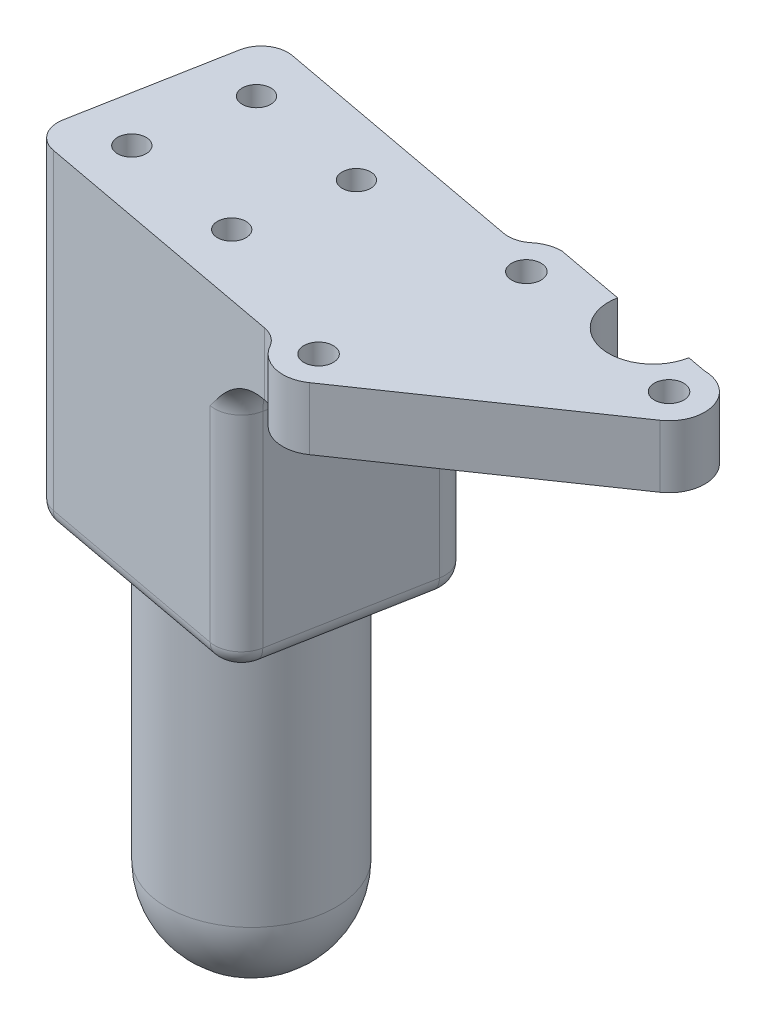
SolidWorks part; units mm, degrees
ref_plane "Front Plane" through (0, 0, 0) normal (0, 0, 1) x (1, 0, 0)
ref_plane "Top Plane" through (0, 0, 0) normal (0, 1, 0) x (1, 0, 0)
ref_plane "Right Plane" through (0, 0, 0) normal (1, 0, 0) x (0, 0, -1)
sketch "Sketch1" plane through (0, 0, 0) normal (0, 1, 0) x (1, 0, 0)
  line L0 (1.4975, 0.7868) -> (-36.9339, 98.5008) construction
  line L6 (-56.6569, 90.4835) -> (-36.9937, 86.8285)
  line L17 (-34.7298, 79.5308) -> (-58.048, 63.5226)
  line L18 (-61.6543, 88.9381) -> (-90.7933, 94.3545)
  line L19 (1.4975, 0.7868) -> (79.9099, 31.6269) construction
  line L20 (-94.291, 91.9533) -> (-97.3978, 75.2396)
  line L21 (-65.8576, 66.3255) -> (-94.9966, 71.7418)
  line L22 (6.159, 94.65) -> (23.8009, 118.4656) construction
  line L23 (9.5157, 132.7811) -> (23.176, 122.6619) construction
  line L24 (-12.3225, 108.3406) -> (5.3194, 132.1562) construction
  line L25 (-25.6246, 83.1119) -> (2.3512, 87.278) construction
  line L26 (-17.0338, 106.0675) -> (-28.9387, 89.9966) construction
  line L27 (59.6519, -88.9099) -> (39.9887, -85.2549) construction
  line L28 (37.7248, -77.9572) -> (61.043, -61.949) construction
  line L29 (64.6494, -87.3645) -> (93.7884, -92.7809) construction
  line L30 (97.2861, -90.3797) -> (100.3929, -73.666) construction
  line L31 (68.8527, -64.7518) -> (97.9916, -70.1682) construction
  line L32 (-3.1639, -93.0764) -> (-20.8058, -116.8919) construction
  line L33 (-6.5207, -131.2074) -> (-20.1809, -121.0883) construction
  line L34 (15.3176, -106.767) -> (-2.3243, -130.5825) construction
  line L35 (28.6196, -81.5383) -> (0.6438, -85.7043) construction
  line L36 (20.0288, -104.4939) -> (31.9337, -88.423) construction
  circle A33 centre (-56.6569, 86.4835) radius 1.65
  circle A34 centre (-36.9937, 82.8285) radius 1.65
  circle A35 centre (-40.6487, 63.1653) radius 1.65 construction
  circle A36 centre (-60.3119, 66.8203) radius 1.65
  arc A37 (-56.6569, 90.4835) -> (-59.1993, 89.5716) centre (-56.6569, 86.4835) ccw
  arc A38 (-34.7298, 79.5308) -> (-36.9937, 86.8285) centre (-36.9937, 82.8285) ccw
  arc A39 (-63.7941, 64.8521) -> (-58.048, 63.5226) centre (-60.3119, 66.8203) ccw
  arc A40 (-65.8576, 66.3255) -> (-63.7941, 64.8521) centre (-66.4058, 63.376) cw
  arc A41 (-59.1993, 89.5716) -> (-61.6543, 88.9381) centre (-61.1061, 91.8876) cw
  arc A42 (-90.7933, 94.3545) -> (-94.291, 91.9533) centre (-91.3416, 91.405) ccw
  arc A43 (-94.9966, 71.7418) -> (-97.3978, 75.2396) centre (-94.4483, 74.6913) cw
  arc A44 (23.8009, 118.4656) -> (23.176, 122.6619) centre (21.3903, 120.2513) ccw construction
  arc A45 (5.3194, 132.1562) -> (9.5157, 132.7811) centre (7.73, 130.3704) cw construction
  arc A46 (-14.5513, 107.1319) -> (-12.3225, 108.3406) centre (-14.7332, 110.1263) ccw construction
  arc A47 (6.159, 94.65) -> (5.6521, 92.1657) centre (8.5696, 92.8643) ccw construction
  arc A48 (5.6521, 92.1657) -> (2.3512, 87.278) centre (1.7621, 91.2343) cw construction
  arc A49 (-25.6246, 83.1119) -> (-28.9387, 89.9966) centre (-26.2137, 87.0683) cw construction
  arc A50 (-17.0338, 106.0675) -> (-14.5513, 107.1319) centre (-14.3088, 103.1392) cw construction
  circle A51 centre (1.7621, 91.2343) radius 1.65 construction
  circle A52 centre (-10.1428, 75.1634) radius 1.65 construction
  circle A53 centre (-26.2137, 87.0683) radius 1.65 construction
  circle A54 centre (-14.3088, 103.1392) radius 1.65 construction
  circle A55 centre (59.6519, -84.9099) radius 1.65 construction
  circle A56 centre (39.9887, -81.2549) radius 1.65 construction
  circle A57 centre (43.6437, -61.5917) radius 1.65 construction
  circle A58 centre (63.3069, -65.2467) radius 1.65 construction
  arc A59 (59.6519, -88.9099) -> (62.1943, -87.9979) centre (59.6519, -84.9099) ccw construction
  arc A60 (37.7248, -77.9572) -> (39.9887, -85.2549) centre (39.9887, -81.2549) ccw construction
  arc A61 (66.7892, -63.2785) -> (61.043, -61.949) centre (63.3069, -65.2467) ccw construction
  arc A62 (68.8527, -64.7518) -> (66.7892, -63.2785) centre (69.4009, -61.8024) cw construction
  arc A63 (62.1943, -87.9979) -> (64.6494, -87.3645) centre (64.1012, -90.314) cw construction
  arc A64 (93.7884, -92.7809) -> (97.2861, -90.3797) centre (94.3366, -89.8314) ccw construction
  arc A65 (97.9916, -70.1682) -> (100.3929, -73.666) centre (97.4434, -73.1177) cw construction
  arc A66 (-20.8058, -116.8919) -> (-20.1809, -121.0883) centre (-18.3952, -118.6777) ccw construction
  arc A67 (-2.3243, -130.5825) -> (-6.5207, -131.2074) centre (-4.7349, -128.7968) cw construction
  arc A68 (17.5464, -105.5582) -> (15.3176, -106.767) centre (17.7282, -108.5527) ccw construction
  arc A69 (-3.1639, -93.0764) -> (-2.657, -90.5921) centre (-5.5746, -91.2907) ccw construction
  arc A70 (-2.657, -90.5921) -> (0.6438, -85.7043) centre (1.233, -89.6607) cw construction
  arc A71 (28.6196, -81.5383) -> (31.9337, -88.423) centre (29.2088, -85.4947) cw construction
  arc A72 (20.0288, -104.4939) -> (17.5464, -105.5582) centre (17.3039, -101.5656) cw construction
  circle A73 centre (1.233, -89.6607) radius 1.65 construction
  circle A74 centre (13.1379, -73.5898) radius 1.65 construction
  circle A75 centre (29.2088, -85.4947) radius 1.65 construction
  circle A76 centre (17.3039, -101.5656) radius 1.65 construction
  dimension "D1" = 8
  dimension "D2" = 8
  dimension "D3" = 8
  dimension "D4" = 3
  dimension "D5" = 3
extrude "Boss-Extrude1" add sketch "Sketch1" along normal mid plane 7
sketch "Sketch3" plane through (0, -3.5, 0) normal (0, 1, 0) x (1, 0, 0)
  line L2 (-69.1638, 90.334) -> (-90.7933, 94.3545)
  line L3 (-61.6543, 88.9381) -> (-90.7933, 94.3545) construction
  line L4 (-94.291, 91.9533) -> (-97.3978, 75.2396)
  line L5 (-94.9966, 71.7418) -> (-73.3671, 67.7213)
  line L6 (-94.9966, 71.7418) -> (-65.8576, 66.3255) construction
  line L7 (-69.8693, 70.1226) -> (-66.7626, 86.8363)
  arc A0 (-90.7933, 94.3545) -> (-94.291, 91.9533) centre (-91.3416, 91.405) ccw
  arc A1 (-97.3978, 75.2396) -> (-94.9966, 71.7418) centre (-94.4483, 74.6913) ccw
  arc A2 (-73.3671, 67.7213) -> (-69.8693, 70.1226) centre (-72.8188, 70.6708) ccw
  arc A3 (-69.1638, 90.334) -> (-66.7626, 86.8363) centre (-69.7121, 87.3845) cw
  point P2 (-70.4176, 67.1731)
  point P19 (-66.2143, 89.7857)
  dimension "D2" = 3
  dimension "D1" = 28
extrude "Boss-Extrude3" add sketch "Sketch3" against normal blind 30
fillet "Fillet1" radius 5 3 edges at (-71.1209, -3.5, -68.1975) (-68.316, -3.5, -78.4794) (-67.2388, -3.5, -89.0824)
fillet "Fillet2" radius 2 8 edges at (-67.2388, -33.5, -89.0824) (-68.316, -33.5, -78.4794) (-71.1209, -33.5, -68.1975) (-84.1818, -33.5, -69.7316) (-96.9216, -33.5, -72.9934) (-95.8444, -33.5, -83.5964) (-93.0395, -33.5, -93.8783) (-79.9786, -33.5, -92.3443)
sketch "Sketch4" plane through (0, -33.5, 0) normal (0, -1, 0) x (-1, 0, 0)
  line L0 (93.8781, 83.2309) -> (70.2823, 78.8449) construction
  line L1 (92.3247, 91.5878) -> (95.4315, 74.8741) construction
  line L2 (71.8357, 70.4881) -> (68.7289, 87.2018) construction
  line L4 (69.5293, 88.3677) -> (91.1588, 92.3882) construction
  line L5 (80.3441, 90.3779) -> (83.8163, 71.6979) construction
  line L6 (94.6311, 73.7082) -> (73.0016, 69.6877) construction
  circle A0 centre (82.0802, 81.0379) radius 9.5
extrude "Boss-Extrude4" add sketch "Sketch4" along normal blind 30
fillet "Fillet3" radius 1 2 edges at (-72.7402, -33.5, -79.3018) (-91.4202, -33.5, -82.7741)
sketch "Sketch5" plane through (0, -63.5, 0) normal (0, -1, 0) x (-1, 0, 0)
  line L0 (82.0802, 90.5379) -> (82.0802, 71.5379) construction
  line L1 (82.0802, 90.5379) -> (82.0802, 71.5379)
  circle A0 centre (82.0802, 81.0379) radius 9.5 construction
  arc A1 (84.4875, 90.2279) -> (76.5313, 88.749) centre (82.0802, 81.0379) ccw construction
  arc A2 (82.0802, 71.5379) -> (82.0802, 90.5379) centre (82.0802, 81.0379) ccw
revolve "Revolve1" add sketch "Sketch5" angle 180 about L0
sketch "Sketch6" plane through (0, 3.5, 0) normal (0, 1, 0) x (1, 0, 0)
  line L0 (-36.9937, 86.8285) -> (-56.6569, 90.4835) construction
  circle A0 centre (-44.0861, 88.1468) radius 5
  dimension "D1" = 10
extrude "Cut-Extrude1" cut sketch "Sketch6" against normal blind 10
sketch "Sketch7" plane through (0, 3.5, 0) normal (0, 1, 0) x (1, 0, 0)
  line L0 (-88.849, 88.3989) -> (-91.042, 76.601) construction
  line L1 (-94.291, 91.9533) -> (-97.3978, 75.2396) construction
  line L2 (-75.0847, 85.8404) -> (-77.2777, 74.0425) construction
  line L3 (-61.6543, 88.9381) -> (-90.7933, 94.3545) construction
  circle A0 centre (-88.849, 88.3989) radius 1.6
  circle A1 centre (-91.042, 76.601) radius 1.6
  circle A2 centre (-75.0847, 85.8404) radius 1.6
  circle A3 centre (-77.2777, 74.0425) radius 1.6
  point P8 (0, 0)
  point P9 (0, 0)
  point P12 (0, 0)
  point P14 (-89.9455, 82.4999)
  point P17 (0, 0)
  dimension "D2" = 3.2
  dimension "D3" = 12
  dimension "D1" = 6
  dimension "D4" = 5.5
  dimension "D5" = 5.5
  dimension "D6" = 12
  dimension "D7" = 14
extrude "Cut-Extrude2" cut sketch "Sketch7" against normal blind 10
